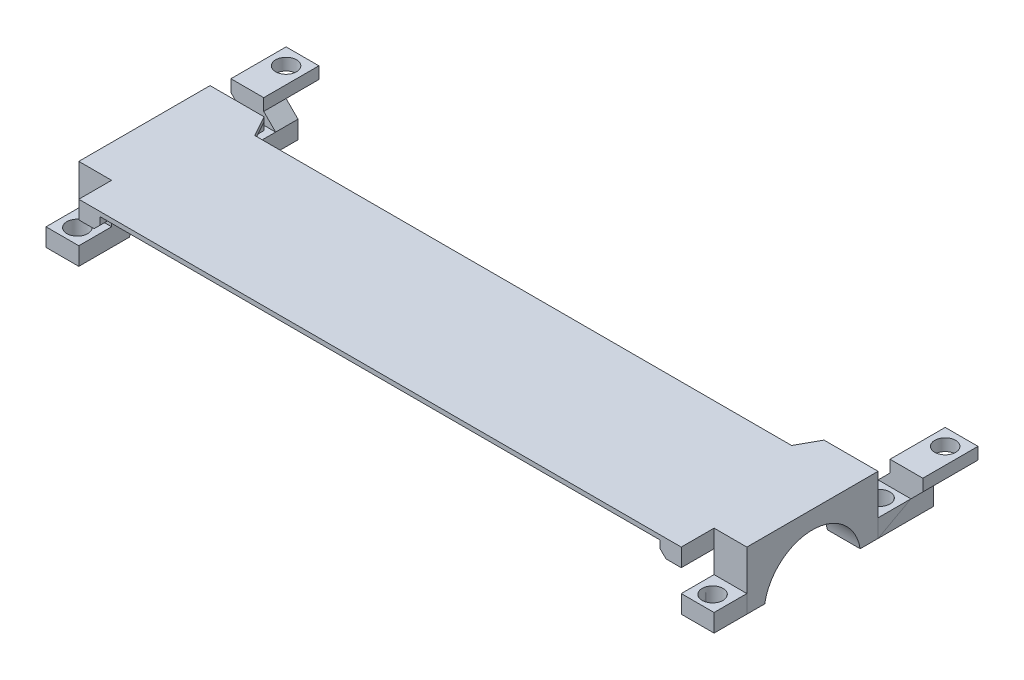
SolidWorks part; units mm, degrees
ref_plane "Alzado" through (0, 0, 0) normal (0, 0, 1) x (1, 0, 0)
ref_plane "Planta" through (0, 0, 0) normal (0, 1, 0) x (1, 0, 0)
ref_plane "Vista lateral" through (0, 0, 0) normal (1, 0, 0) x (0, 0, -1)
sketch "Croquis1" plane through (0, 0, 0) normal (0, 1, 0) x (1, 0, 0)
  line L1 (-56, 16.5) -> (56, 16.5)
  line L2 (-56, 16.5) -> (-56, -16.5)
  line L3 (-56, -16.5) -> (56, -16.5)
  line L4 (56, 16.5) -> (56, -16.5)
  line L5 (-56, 16.5) -> (56, -16.5) construction
  line L6 (-56, -16.5) -> (56, 16.5) construction
  point P0 (0, 0)
  dimension "D1" = 112
  dimension "D2" = 33
extrude "Saliente-Extruir1" add sketch "Croquis1" along normal blind 0.75
sketch "Croquis2" plane through (0, 0.75, 0) normal (0, 1, 0) x (1, 0, 0)
  line L1 (-53.25, 14) -> (53.25, 14)
  line L2 (-53.25, 14) -> (-53.25, -14)
  line L3 (-53.25, -14) -> (53.25, -14)
  line L4 (53.25, 14) -> (53.25, -14)
  line L5 (-53.25, 14) -> (53.25, -14) construction
  line L6 (-53.25, -14) -> (53.25, 14) construction
  circle A0 centre (-53.25, 14) radius 1.75
  circle A1 centre (-53.25, -14) radius 1.75
  circle A2 centre (53.25, -14) radius 1.75
  circle A3 centre (53.25, 14) radius 1.75
  point P1 (0, 0)
  dimension "D3" = 3.5
  dimension "D1" = 106.5
  dimension "D2" = 28
extrude "Cortar-Extruir1" cut sketch "Croquis2" against normal blind 0.75 contours L1 A0 L2 | L2 A0 L1 | L2 A1 L3 | L3 A1 L2 | L4 A3 L1 | L1 A3 L4 | L3 A2 L4 | L4 A2 L3 region at (-53.4976, 0.75, -14.2476) region at (-52.5073, 0.75, -13.2573) region at (53.4976, 0.75, -14.2476) region at (52.5073, 0.75, -13.2573) region at (-52.5073, 0.75, 13.2573) region at (-53.4976, 0.75, 14.2476) region at (53.4976, 0.75, 14.2476) region at (52.5073, 0.75, 13.2573)
sketch "Croquis3" plane through (0, 0.75, 0) normal (0, 1, 0) x (1, 0, 0)
  line L0 (-56, -16.5) -> (56, -16.5) construction
  line L1 (45, 7.5) -> (-45, 7.5)
  line L2 (45, 7.5) -> (45, -16.5)
  line L3 (45, -16.5) -> (-45, -16.5)
  line L4 (-45, 7.5) -> (-45, -16.5)
  line L5 (45, 7.5) -> (-45, -16.5) construction
  line L6 (45, -16.5) -> (-45, 7.5) construction
  line L7 (56, 16.5) -> (-56, 16.5) construction
  line L8 (-56, -16.5) -> (56, -16.5)
  line L9 (56, 16.5) -> (-56, 16.5)
  line L10 (-45, 7.5) -> (-50, 16.5)
  line L11 (-45, -16.5) -> (-50, -16.5)
  line L12 (45, 7.5) -> (50, 16.5)
  line L13 (45, -16.5) -> (50, -16.5)
  point P0 (0, -4.5)
  dimension "D1" = 24
  dimension "D2" = 90
  dimension "D3" = 5
  dimension "D4" = 5
  dimension "D5" = 5
  dimension "D6" = 5
  dimension "D7" = 0
extrude "Cortar-Extruir2" cut sketch "Croquis3" against normal blind 0.75 contours L1 L12 L9 L10 region at (0, 0.75, -12.0789)
ref_plane "Plano1" through (0, -9, 0) normal (0, -1, 0) x (-1, 0, 0)
sketch "Croquis4" plane through (0, -9, 0) normal (0, -1, 0) x (-1, 0, 0)
  line L0 (50.5, 16.5) -> (50.5, 11)
  line L1 (50.5, 11) -> (56, 11)
  line L2 (56, 0) -> (54.0556, 0)
  line L3 (50.5, -11) -> (56, -11)
  line L4 (53.25, 14) -> (-53.25, 14)
  line L5 (-53.25, 14) -> (-53.25, -14)
  line L6 (-53.25, -14) -> (53.25, -14)
  line L7 (53.25, -14) -> (53.25, 14)
  line L8 (53.25, 14) -> (-53.25, 14)
  line L9 (-53.25, 14) -> (-53.25, -14)
  line L10 (-53.25, -14) -> (53.25, -14)
  line L11 (53.25, -14) -> (53.25, 14)
  line L12 (50.5, -16.5) -> (50.5, -11)
  line L13 (0, 7.5) -> (0, 4.9982)
  line L14 (-50.5, -16.5) -> (-50.5, -11)
  line L15 (-50.5, -11) -> (-56, -11)
  line L16 (50, 16.5) -> (45, 7.5)
  line L17 (45, 7.5) -> (-45, 7.5)
  line L18 (-45, 7.5) -> (-50, 16.5)
  line L19 (-50, 16.5) -> (-56, 16.5)
  line L20 (-56, 16.5) -> (-56, -16.5)
  line L21 (-56, -16.5) -> (56, -16.5)
  line L22 (56, -16.5) -> (56, 16.5)
  line L23 (56, 16.5) -> (50, 16.5)
  line L24 (50, 16.5) -> (45, 7.5)
  line L25 (45, 7.5) -> (-45, 7.5)
  line L26 (-45, 7.5) -> (-50, 16.5)
  line L27 (-50, 16.5) -> (-56, 16.5)
  line L28 (-56, 16.5) -> (-56, -16.5)
  line L29 (-56, -16.5) -> (56, -16.5)
  line L30 (56, -16.5) -> (56, 16.5)
  line L31 (56, 16.5) -> (50, 16.5)
  line L32 (-50.5, 11) -> (-56, 11)
  line L33 (-50.5, 16.5) -> (-50.5, 11)
  circle A1 centre (-53.25, 14) radius 1.75
  circle A2 centre (-53.25, 14) radius 1.75
  circle A3 centre (-53.25, -14) radius 1.75
  circle A4 centre (-53.25, -14) radius 1.75
  circle A5 centre (53.25, -14) radius 1.75
  circle A6 centre (53.25, -14) radius 1.75
  circle A7 centre (53.25, 14) radius 1.75
  circle A8 centre (53.25, 14) radius 1.75
  dimension "D7" = 2.75
  dimension "D8" = 5.5
  dimension "D1" = 0
  dimension "D2" = 0
  dimension "D3" = 0
  dimension "D4" = 0
  dimension "D5" = 0
  dimension "D6" = 0
extrude "Saliente-Extruir2" add sketch "Croquis4" against normal blind 3 separate body contours A2 L8 L33 L27 L28 L32 L9 | A2 L9 L32 L33 L8 | A4 L9 L15 L28 L29 L14 L10 | A4 L10 L14 L15 L9 | A8 L11 L1 L30 L31 L0 L8 | A8 L8 L0 L1 L11 | A6 L10 L12 L29 L30 L3 L11 | A6 L11 L3 L12 L10 region at (-53.25, -9, -16.4222) region at (-51.6148, -9, -12.1884) region at (-51.6148, -9, 12.1884) region at (-54.625, -9, 11.0778) region at (51.6148, -9, -12.1884) region at (51, -9, -14.0778) region at (50.5778, -9, 15.25) region at (51.6148, -9, 12.1884)
sketch "Croquis5" plane through (0, 0, 11) normal (0, 0, -1) x (-1, 0, 0)
  line L0 (56, 0.75) -> (-56, 0.75) construction
  line L1 (56, -9) -> (50.5, -9)
  line L2 (56, -9) -> (56, 0.75)
  line L3 (56, 0.75) -> (50.5, 0.75)
  line L4 (50.5, -9) -> (50.5, 0.75)
  line L5 (50.5, -6) -> (56, -6) construction
extrude "Saliente-Extruir3" add sketch "Croquis5" along normal blind 3
mirror "Simetría1" about plane through (0, 0, 0) normal (0, 0, 1) of "Saliente-Extruir3"
mirror "Simetría2" about plane through (0, 0, 0) normal (1, 0, 0) of "Simetría1"
sketch "Croquis6" plane through (0, 0, 0) normal (0, -1, 0) x (1, 0, 0)
  line L4 (-56, 11) -> (-50.5, 11)
  line L5 (-56, 16.5) -> (-56, 11)
  line L6 (-50.5, 16.5) -> (-56, 16.5)
  line L7 (-50.5, 11) -> (-50.5, 16.5)
  line L8 (-56, 11) -> (-50.5, 11)
  line L9 (-56, 16.5) -> (-56, 11)
  line L10 (-50.5, 16.5) -> (-56, 16.5)
  line L11 (-50.5, 11) -> (-50.5, 16.5)
  dimension "D1" = 0
extrude "Cortar-Extruir3" cut sketch "Croquis6" against normal blind 0.75
mirror "Simetría3" about plane through (0, 0, 0) normal (0, 0, 1) of "Cortar-Extruir3"
mirror "Simetría4" about plane through (0, 0, 0) normal (1, 0, 0) of "Simetría3"
ref_plane "Plano2" through (0, -4, 0) normal (0, -1, 0) x (-1, 0, 0)
sketch "Croquis7" plane through (0, -4, 0) normal (0, -1, 0) x (-1, 0, 0)
  line L0 (45, 7.5) -> (50, 16.5)
  line L1 (50, 16.5) -> (50.5, 16.5)
  line L2 (50.5, 16.5) -> (50.5, 11)
  line L3 (45, 7.5) -> (50.5, 11)
  line L5 (58, 25.75) -> (52.5, 25.75)
  line L6 (58, 25.75) -> (58, 20.25)
  line L7 (58, 20.25) -> (52.5, 20.25)
  line L8 (52.5, 25.75) -> (52.5, 20.25)
  line L9 (58, 25.75) -> (52.5, 20.25) construction
  line L10 (58, 20.25) -> (52.5, 25.75) construction
  circle A0 centre (53.25, 14) radius 1.75 construction
  circle A1 centre (53.25, 14) radius 1.75
  circle A2 centre (55.25, 23) radius 1.75
  dimension "D1" = 3.5
  dimension "D2" = 9
  dimension "D3" = 2
  dimension "D4" = 5.5
extrude "Saliente-Extruir4" add sketch "Croquis7" against normal blind 2 separate body contours L6 L7 L8 L5
sketch "Croquis8" plane through (0, -2, 0) normal (0, 1, 0) x (1, 0, 0)
  line L2 (-58, 20.25) -> (-52.5, 20.25) construction
  line L3 (-58, 25.75) -> (-58, 20.25) construction
  circle A0 centre (-55.25, 23) radius 1.75
  dimension "D3" = 3.5
  dimension "D1" = 2.75
  dimension "D2" = 2.75
extrude "Cortar-Extruir4" cut sketch "Croquis8" against normal blind 2
sketch "Croquis9" plane through (0, 0, -16.5) normal (0, 0, -1) x (-1, 0, 0)
  line L0 (50.5, -9) -> (50.5, -6)
  line L1 (50.5, -6) -> (52.5, -4)
  line L2 (-3.025, -4) -> (3.025, -4) construction
  line L3 (52.5, -2) -> (52.5, -4) construction
  line L4 (52.5, -4) -> (58, -4)
  line L5 (58, -4) -> (56, -6)
  line L6 (56, -6) -> (50.5, -6)
  line L7 (52.5, -2) -> (58, -2)
  line L8 (58, -2) -> (58, -4)
  line L9 (52.5, -4) -> (52.5, -2)
  line L10 (50.5, -9) -> (56, -9)
  line L11 (56, -9) -> (56, -6)
  line M5 (50.5, -9) -> (56, -9)
  line M6 (56, -9) -> (56, -6)
  line M7 (56, -6) -> (50.5, -6)
  line M8 (50.5, -6) -> (50.5, -9)
extrude "Saliente-Extruir5" add sketch "Croquis9" along normal up to surface (3.75 mm away) contours M8 M5 M6 M7 | L5 L4 L1 M7 | L9 L4 L8 L7 region at (-53.25, -7.5, -16.5) region at (-54.25, -5, -16.5) region at (-55.25, -3, -16.5) up to face at (-55.25, -3, -20.25)
sketch "Croquis10" plane through (0, 0.75, 0) normal (0, 1, 0) x (1, 0, 0)
  line L0 (-50.5, 16.5) -> (-50, 16.5)
  line L1 (-50, 16.5) -> (-46.9444, 11)
  line L2 (-45, 7.5) -> (-50, 16.5) construction
  line L3 (-46.9444, 11) -> (-50.5, 11)
  line L4 (-50.5, 11) -> (-50.5, 16.5)
extrude "Cortar-Extruir5" cut sketch "Croquis10" against normal blind 0.75
mirror "Simetría5" about plane through (0, 0, 0) normal (1, 0, 0) of "Cortar-Extruir5"
mirror "Simetría9" about plane through (0, 0, 0) normal (1, 0, 0) of bodies 121
sketch "Croquis11" plane through (0, 0, 0) normal (0, -1, 0) x (1, 0, 0)
  line L0 (-56, -8) -> (-50.5, -8)
  line L1 (-50.5, -8) -> (-50.5, -11)
  line L2 (-50.5, -11) -> (-46.9444, -11)
  line L3 (-46.9444, -11) -> (-46.9444, 16.5)
  line L4 (-50.5, 16.5) -> (50.5, 16.5) construction
  line L5 (-46.9444, 16.5) -> (-50.5, 16.5)
  line L6 (-50.5, 16.5) -> (-50.5, 8)
  line L7 (-50.5, 8) -> (-56, 8)
  line L8 (-56, 8) -> (-56, -8)
extrude "Saliente-Extruir6" add sketch "Croquis11" along normal blind 2.25
mirror "Simetría10" about plane through (0, 0, 0) normal (1, 0, 0) of "Saliente-Extruir6"
chamfer "Chaflán1" distance 1 angle 45 2 edges at (46.9444, -2.25, 2.75) (-46.9444, -2.25, 2.75)
sketch "Croquis12" plane through (56, 0, 0) normal (1, 0, 0) x (0, 0, -1)
  line L0 (-8, -2.25) -> (8, -2.25) construction
  line L1 (-8, -9) -> (-8, -2.25)
  line L2 (-8, -2.25) -> (8, -2.25)
  line L3 (8, -2.25) -> (8, -9)
  arc A0 (-8, -9) -> (8, -9) centre (0, -10.3657) cw
  point P0 (0, -2.25)
  line M6 (-8, -9) -> (-8, -2.25)
  line M7 (-8, -2.25) -> (8, -2.25)
  line M8 (8, -2.25) -> (8, -9)
extrude "Saliente-Extruir7" add sketch "Croquis12" against normal blind 5.5 contours A0 M6 M7 | L2 A0 M8 region at (56, -3.9502, -6.1928) region at (56, -3.9502, 6.1928)
mirror "Simetría11" about plane through (0, 0, 0) normal (1, 0, 0) of "Saliente-Extruir7"
